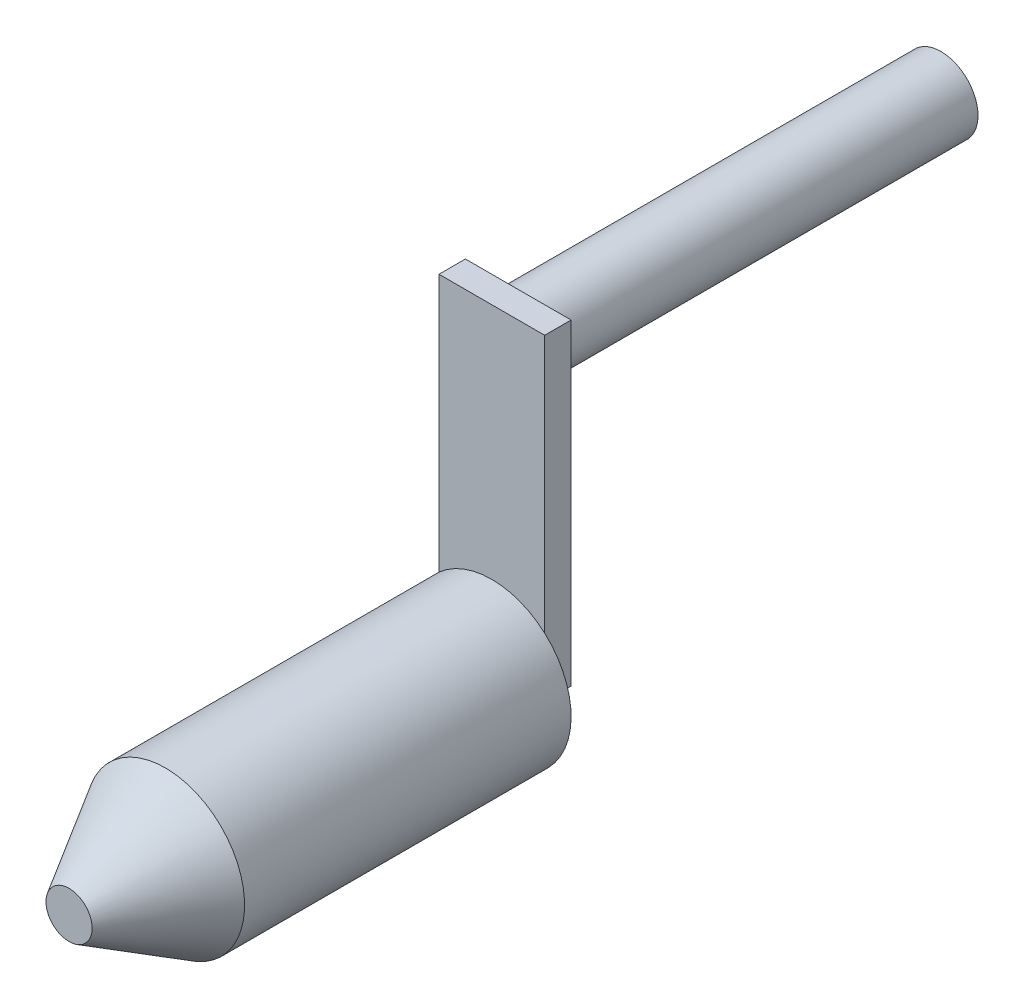
SolidWorks part; units mm, degrees
ref_plane "Front Plane" through (0, 0, 0) normal (0, 0, 1) x (1, 0, 0)
ref_plane "Top Plane" through (0, 0, 0) normal (0, 1, 0) x (1, 0, 0)
ref_plane "Right Plane" through (0, 0, 0) normal (1, 0, 0) x (0, 0, -1)
sketch "Sketch1" plane through (0, 0, 0) normal (0, 0, 1) x (1, 0, 0)
  circle A0 centre (0, 0) radius 9.525
  dimension "D1" = 19.05
extrude "Boss-Extrude1" add sketch "Sketch1" along normal blind 50.8
sketch "Sketch2" plane through (0, 0, 0) normal (0, 0, -1) x (-1, 0, 0)
  line L1 (-6.35, 0) -> (6.35, 0)
  line L2 (-6.35, 0) -> (-6.35, 38.1)
  line L3 (-6.35, 38.1) -> (6.35, 38.1)
  line L4 (6.35, 0) -> (6.35, 38.1)
  point P0 (0, 0)
  point P7 (0, 0)
  dimension "D1" = 12.7
  dimension "D2" = 38.1
extrude "Boss-Extrude2" add sketch "Sketch2" along normal blind 3.175
sketch "Sketch3" plane through (0, 0, -3.175) normal (0, 0, -1) x (-1, 0, 0)
  line L0 (0, 33.02) -> (0, 0) construction
  circle A0 centre (0, 33.02) radius 4.445
  dimension "D1" = 8.89
  dimension "D2" = 33.02
extrude "Boss-Extrude3" add sketch "Sketch3" along normal blind 50.8
sketch "Sketch4" plane through (0, 0, 0) normal (1, 0, 0) x (0, 0, -1)
  line L0 (-50.8, 2.7713) -> (-39.2321, 9.525)
  line L1 (-50.8, 9.525) -> (-50.8, -9.525) construction
  line L2 (-39.2321, 9.525) -> (-50.8, 9.525)
  line L3 (-50.8, 9.525) -> (-50.8, 2.7713)
  line L4 (0.7894, 0) -> (-54.9671, 0) construction
revolve "Cut-Revolve1" cut sketch "Sketch4" angle 360 about L4
ref_point "Point1"
ref_axis "Axis1" through (0, 0, 39.2321) along (0, 0, -1)
